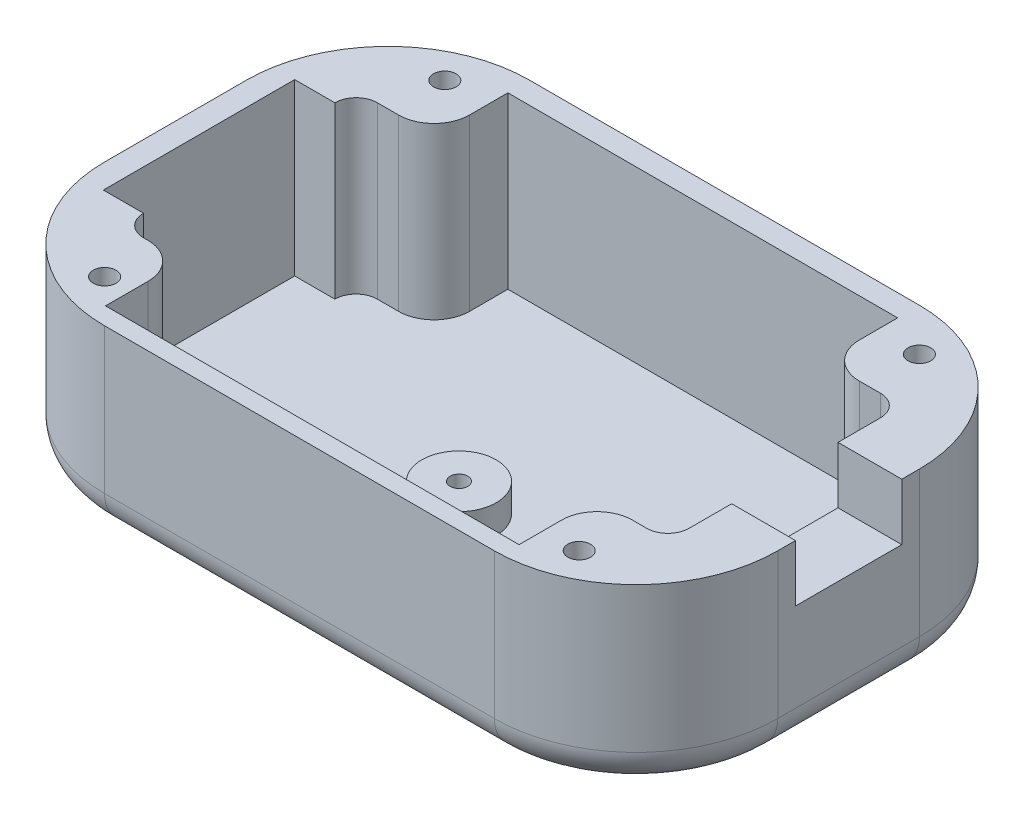
SolidWorks part; units mm, degrees
ref_plane "Front Plane" through (0, 0, 0) normal (0, 0, 1) x (1, 0, 0)
ref_plane "Top Plane" through (0, 0, 0) normal (0, 1, 0) x (1, 0, 0)
ref_plane "Right Plane" through (0, 0, 0) normal (1, 0, 0) x (0, 0, -1)
sketch "Sketch2" plane through (0, 0, 0) normal (0, 1, 0) x (1, 0, 0)
  line L0 (38.5, 0) -> (-38.5, 0) construction
  line L1 (-27.5, 30) -> (27.5, 30)
  line L2 (-47.5, 10) -> (-47.5, -10)
  line L3 (-27.5, -30) -> (27.5, -30)
  line L4 (47.5, 10) -> (47.5, -10)
  line L5 (-47.5, 30) -> (47.5, -30) construction
  line L6 (-47.5, -30) -> (47.5, 30) construction
  line L7 (-35.5, 16.5) -> (35.5, 16.5)
  line L8 (-38.5, 13.5) -> (-38.5, -13.5)
  line L9 (-35.5, -16.5) -> (35.5, -16.5)
  line L10 (38.5, 13.5) -> (38.5, -13.5)
  line L11 (-38.5, 16.5) -> (38.5, -16.5) construction
  line L12 (-38.5, -16.5) -> (38.5, 16.5) construction
  line L13 (0, 0) -> (0, 8.176) construction
  line L15 (-12, -27.5) -> (12, -27.5)
  line L16 (-12, -27.5) -> (-12, -13.5)
  line L17 (-12, -13.5) -> (12, -13.5)
  line L18 (12, -27.5) -> (12, -13.5)
  line L19 (-12, -27.5) -> (12, -13.5) construction
  line L20 (-12, -13.5) -> (12, -27.5) construction
  arc A0 (27.5, 30) -> (47.5, 10) centre (27.5, 10) cw
  arc A1 (27.5, -30) -> (47.5, -10) centre (27.5, -10) ccw
  arc A2 (-47.5, -10) -> (-27.5, -30) centre (-27.5, -10) ccw
  arc A3 (-27.5, 30) -> (-47.5, 10) centre (-27.5, 10) ccw
  arc A4 (35.5, 16.5) -> (38.5, 13.5) centre (35.5, 13.5) cw
  arc A5 (35.5, -16.5) -> (38.5, -13.5) centre (35.5, -13.5) ccw
  arc A6 (-38.5, -13.5) -> (-35.5, -16.5) centre (-35.5, -13.5) ccw
  arc A7 (-35.5, 16.5) -> (-38.5, 13.5) centre (-35.5, 13.5) ccw
  circle A8 centre (22, -4) radius 1.25
  circle A9 centre (-3.4806, -4) radius 1.25
  circle A10 centre (-33.4806, 24) radius 1.6
  circle A11 centre (33.4806, 24) radius 1.6
  circle A12 centre (33.4806, -24) radius 1.6
  circle A13 centre (-33.4806, -24) radius 1.6
  point P0 (0, 0)
  point P18 (0, 0)
  point P55 (0, -20.5)
  point P56 (0, 0)
  point P57 (0, 0)
  point P58 (-3.4806, -3.4011)
  point P59 (22, -4.4636)
  point P62 (16.1275, -4.7534)
  dimension "D3" = 20
  dimension "D6" = 3
  dimension "D7" = 2.5
  dimension "D9" = 2.5
  dimension "D11" = 3.2
  dimension "D18" = 4
  dimension "D1" = 60
  dimension "D2" = 95
  dimension "D4" = 33
  dimension "D5" = 77
  dimension "D8" = 16.5
  dimension "D10" = 4
  dimension "D12" = 24
  dimension "D13" = 30
  dimension "D14" = 24
  dimension "D15" = 14
  dimension "D16" = 12
  dimension "D17" = 2.5
  dimension "D19" = 25.4806
extrude "Boss-Extrude1" add sketch "Sketch2" along normal blind 1.5 contours L1 A3 L2 A2 L3 A1 L4 A0 A11 A10 A7 L7 A4 L10 A5 L9 L18 L15 L16 A6 L8 A12 A13 | L15 L18 L9 L16 | L9 L18 L17 L16 | L7 A7 L8 A6 L9 L16 L17 L18 A5 L10 A4 A9 A8 region at (0, 0, -28.8764) region at (-0.0371, 0, -0.4566) region at (0, 0, 15) region at (0, 0, 22)
extrude "Boss-Extrude2" add sketch "Sketch2<3>" along normal blind 24 from surface contours L1 A3 L2 A2 L3 A1 L4 A0 A11 A10 A7 L7 A4 L10 A5 L9 L18 L15 L16 A6 L8 A12 A13 region at (0, 0, -28.8764) starting at face at (33.4806, 1.5, -22.4)
sketch "Sketch2<3>" plane through (0, 0, 0) normal (0, 1, 0) x (1, 0, 0) same geometry as "Sketch2"
sketch "Sketch3" plane through (0, 1.5, 0) normal (0, 1, 0) x (1, 0, 0)
  circle A2 centre (-3.4806, -4) radius 5.25
  circle A3 centre (-3.4806, -4) radius 5.25
  circle A4 centre (22, -4) radius 1.25 construction
  circle A5 centre (22, -4) radius 5.25
  circle A6 centre (22, -4) radius 5.25
  circle A7 centre (-3.4806, -4) radius 1.25 construction
  circle A8 centre (22, -4) radius 1.25
  circle A9 centre (-3.4806, -4) radius 1.25
  dimension "D1" = 4
  dimension "D2" = 4
extrude "Boss-Extrude3" add sketch "Sketch3" along normal blind 4
fillet "Fillet1" radius 10 2 edges at (12, 13.5, 16.5) (-12, 13.5, 16.5)
sketch "Sketch4" plane through (0, 1.5, 0) normal (0, 1, 0) x (1, 0, 0)
  line L0 (0, -27.5) -> (0, -11.9552) construction
  line L1 (12, -27.5) -> (-12, -27.5) construction
  line L2 (-7, -17.5) -> (7, -17.5) construction
  line L3 (12, -27.5) -> (-12, -27.5) construction
  circle A0 centre (-7, -17.5) radius 1.3
  circle A1 centre (7, -17.5) radius 1.3
  dimension "D4" = 2.6
  dimension "D5" = 2.6
  dimension "D1" = 14
  dimension "D2" = 10
  dimension "D3" = 7
extrude "Cut-Extrude1" cut sketch "Sketch4" against normal blind 7
sketch "Sketch5" plane through (0, 0, 0) normal (0, -1, 0) x (1, 0, 0)
  circle A2 centre (-33.4806, 24) radius 3.1
  circle A3 centre (-33.4806, 24) radius 3.1
  circle A5 centre (-33.4806, -24) radius 3.1
  circle A6 centre (-33.4806, -24) radius 3.1
  circle A8 centre (33.4806, -24) radius 3.1
  circle A9 centre (33.4806, -24) radius 3.1
  circle A11 centre (33.4806, 24) radius 3.1
  circle A12 centre (33.4806, 24) radius 3.1
  dimension "D1" = 1.5
  dimension "D2" = 1.5
  dimension "D3" = 1.5
  dimension "D4" = 1.5
extrude "Cut-Extrude2" cut sketch "Sketch5" against normal blind 15
fillet "Fillet2" radius 5 8 edges at (-47.5, 0, 0) (-41.6421, 0, -24.1421) (0, 0, -30) (41.6421, 0, -24.1421) (47.5, 0, 0) (41.6421, 0, 24.1421) (0, 0, 30) (-41.6421, 0, 24.1421)
sketch "Sketch6" plane through (47.5, 0, 0) normal (1, 0, 0) x (0, 0, -1)
  line L0 (-30, 17.5) -> (30, 17.5) construction
  line L1 (-30, 25.5) -> (-30, 5) construction
  line L2 (30, 25.5) -> (30, 5) construction
  line L3 (1.25, 5.5) -> (-9.25, 5.5) construction
  line L4 (-30, 26.5) -> (30, 26.5) construction
  line L6 (-7.5, 26.5) -> (7.5, 26.5)
  line L7 (-7.5, 26.5) -> (-7.5, 17.5)
  line L8 (-7.5, 17.5) -> (7.5, 17.5)
  line L9 (7.5, 26.5) -> (7.5, 17.5)
  line L10 (-7.5, 26.5) -> (7.5, 17.5) construction
  line L11 (-7.5, 17.5) -> (7.5, 26.5) construction
  point P14 (0, 22)
  dimension "D1" = 12
  dimension "D2" = 9
  dimension "D3" = 15
  dimension "D4" = 7.5
extrude "Cut-Extrude3" cut sketch "Sketch6" against normal blind 15
sketch "Sketch7" plane through (0, 25.5, 0) normal (0, 1, 0) x (1, 0, 0)
  line L0 (35.5, -16.5) -> (22, -16.5) construction
  line L1 (28.5, -16.5) -> (16.5, -16.5)
  line L2 (28.5, -16.5) -> (28.5, -22.5)
  line L3 (28.5, -22.5) -> (16.5, -22.5)
  line L4 (16.5, -16.5) -> (16.5, -22.5)
  line L5 (28.5, -16.5) -> (16.5, -22.5) construction
  line L6 (28.5, -22.5) -> (16.5, -16.5) construction
  line L7 (38.5, -13.5) -> (38.5, 13.5) construction
  point P4 (22.5, -19.5)
  dimension "D1" = 10
  dimension "D2" = 12
extrude "Cut-Extrude4" cut sketch "Sketch7" against normal blind 15
sketch "Sketch10" plane through (0, 25.5, 0) normal (0, 1, 0) x (1, 0, 0)
  line L1 (-27.5, 16.5) -> (27.5, 16.5)
  line L2 (-27.5, 16.5) -> (-27.5, 26.9174)
  line L3 (-27.5, 26.9174) -> (27.5, 26.9174)
  line L4 (27.5, 16.5) -> (27.5, 26.9174)
  line L5 (-27.5, 16.5) -> (27.5, 26.9174) construction
  line L6 (-27.5, 26.9174) -> (27.5, 16.5) construction
  line L7 (-38.5, 13.5) -> (-44.1621, 13.5)
  line L8 (-38.5, 13.5) -> (-38.5, -13.5)
  line L9 (-38.5, -13.5) -> (-44.1621, -13.5)
  line L10 (-44.1621, 13.5) -> (-44.1621, -13.5)
  line L11 (-38.5, 13.5) -> (-44.1621, -13.5) construction
  line L12 (-38.5, -13.5) -> (-44.1621, 13.5) construction
  line L13 (-29.8564, -16.5) -> (-12, -16.5)
  line L14 (-29.8564, -16.5) -> (-29.8564, -27.5)
  line L15 (-29.8564, -27.5) -> (-12, -27.5)
  line L16 (-12, -16.5) -> (-12, -27.5)
  line L17 (-29.8564, -16.5) -> (-12, -27.5) construction
  line L18 (-29.8564, -27.5) -> (-12, -16.5) construction
  line L19 (28.5, -16.5) -> (28.5, -22.5)
  line L20 (28.5, -22.5) -> (16.5, -22.5)
  line L21 (16.5, -22.5) -> (16.5, -18.1484)
  line L22 (12, -26.5) -> (12, -27.5)
  line L23 (12, -27.5) -> (-12, -27.5)
  line L24 (-12, -27.5) -> (-12, -26.5)
  line L25 (-22, -16.5) -> (-35.5, -16.5)
  line L26 (-38.5, -13.5) -> (-38.5, 13.5)
  line L27 (-35.5, 16.5) -> (35.5, 16.5)
  line L28 (38.5, 13.5) -> (38.5, 7.5)
  line L29 (38.5, 7.5) -> (47.5, 7.5)
  line L30 (47.5, 7.5) -> (47.5, 10)
  line L31 (27.5, 30) -> (-27.5, 30)
  line L32 (-47.5, 10) -> (-47.5, -10)
  line L33 (-27.5, -30) -> (27.5, -30)
  line L34 (47.5, -10) -> (47.5, -7.5)
  line L35 (47.5, -7.5) -> (38.5, -7.5)
  line L36 (38.5, -7.5) -> (38.5, -13.5)
  line L37 (35.5, -16.5) -> (28.5, -16.5)
  line L38 (28.5, -16.5) -> (28.5, -22.5)
  line L39 (28.5, -22.5) -> (16.5, -22.5)
  line L40 (16.5, -22.5) -> (16.5, -18.1484)
  line L41 (12, -26.5) -> (12, -27.5)
  line L42 (12, -27.5) -> (-12, -27.5)
  line L43 (-12, -27.5) -> (-12, -26.5)
  line L44 (-22, -16.5) -> (-35.5, -16.5)
  line L45 (-38.5, -13.5) -> (-38.5, 13.5)
  line L46 (-35.5, 16.5) -> (35.5, 16.5)
  line L47 (38.5, 13.5) -> (38.5, 7.5)
  line L48 (38.5, 7.5) -> (47.5, 7.5)
  line L49 (47.5, 7.5) -> (47.5, 10)
  line L50 (27.5, 30) -> (-27.5, 30)
  line L51 (-47.5, 10) -> (-47.5, -10)
  line L52 (-27.5, -30) -> (27.5, -30)
  line L53 (47.5, -10) -> (47.5, -7.5)
  line L54 (47.5, -7.5) -> (38.5, -7.5)
  line L55 (38.5, -7.5) -> (38.5, -13.5)
  line L56 (35.5, -16.5) -> (28.5, -16.5)
  line L57 (12, -27.5) -> (28.5, -27.5)
  line L58 (12, -27.5) -> (12, -16.5)
  line L59 (12, -16.5) -> (28.5, -16.5)
  line L60 (28.5, -27.5) -> (28.5, -16.5)
  line L61 (12, -27.5) -> (28.5, -16.5) construction
  line L62 (12, -16.5) -> (28.5, -27.5) construction
  arc A10 (16.5, -18.1484) -> (12, -26.5) centre (22, -26.5) ccw
  arc A11 (-12, -26.5) -> (-22, -16.5) centre (-22, -26.5) ccw
  arc A12 (-38.5, -13.5) -> (-35.5, -16.5) centre (-35.5, -13.5) ccw
  arc A13 (-35.5, 16.5) -> (-38.5, 13.5) centre (-35.5, 13.5) ccw
  arc A14 (38.5, 13.5) -> (35.5, 16.5) centre (35.5, 13.5) ccw
  arc A15 (47.5, 10) -> (27.5, 30) centre (27.5, 10) ccw
  arc A16 (-27.5, 30) -> (-47.5, 10) centre (-27.5, 10) ccw
  arc A17 (-47.5, -10) -> (-27.5, -30) centre (-27.5, -10) ccw
  arc A18 (27.5, -30) -> (47.5, -10) centre (27.5, -10) ccw
  arc A19 (35.5, -16.5) -> (38.5, -13.5) centre (35.5, -13.5) ccw
  arc A20 (16.5, -18.1484) -> (12, -26.5) centre (22, -26.5) ccw
  arc A21 (-12, -26.5) -> (-22, -16.5) centre (-22, -26.5) ccw
  arc A22 (-38.5, -13.5) -> (-35.5, -16.5) centre (-35.5, -13.5) ccw
  arc A23 (-35.5, 16.5) -> (-38.5, 13.5) centre (-35.5, 13.5) ccw
  arc A24 (38.5, 13.5) -> (35.5, 16.5) centre (35.5, 13.5) ccw
  arc A25 (47.5, 10) -> (27.5, 30) centre (27.5, 10) ccw
  arc A26 (-27.5, 30) -> (-47.5, 10) centre (-27.5, 10) ccw
  arc A27 (-47.5, -10) -> (-27.5, -30) centre (-27.5, -10) ccw
  arc A28 (27.5, -30) -> (47.5, -10) centre (27.5, -10) ccw
  arc A29 (35.5, -16.5) -> (38.5, -13.5) centre (35.5, -13.5) ccw
  point P17 (0, 21.7087)
  point P27 (-41.331, 0)
  point P51 (-20.9282, -22)
  point P54 (20.25, -22)
  line M30 (28.5, -16.5) -> (28.5, -22.5)
  line M31 (28.5, -22.5) -> (16.5, -22.5)
  line M32 (16.5, -22.5) -> (16.5, -18.1484)
  arc M33 (16.5, -18.1484) -> (12, -26.5) centre (22, -26.5) ccw
  line M34 (12, -26.5) -> (12, -27.5)
  line M36 (-12, -27.5) -> (-12, -26.5)
  arc M37 (-12, -26.5) -> (-22, -16.5) centre (-22, -26.5) ccw
  line M38 (-22, -16.5) -> (-35.5, -16.5)
  line M40 (-38.5, -13.5) -> (-38.5, 13.5)
  line M42 (-35.5, 16.5) -> (35.5, 16.5)
  dimension "D1" = 0
extrude "Cut-Extrude5" cut sketch "Sketch10" against normal up to surface (24 mm away) contours L7 L10 L9 M40 | L4 L3 L2 M42 | L14 L15 M36 M37 M38 | L16 L13 M37 | L59 L58 M33 M32 M31 M30 | L57 L60 M31 M32 M33 M34 region at (0, 25.5, -21.7087) region at (-41.331, 25.5, 0) region at (-21.7493, 25.5, 22.4006) region at (-14.2337, 25.5, 18.7337) region at (19.8115, 25.5, 24.589) region at (20.6904, 25.5, 19.3993) up to face at (-7, 1.5, 18.8)
fillet "Fillet6" radius 5 4 edges at (27.5, 13.5, -16.5) (28.5, 13.5, 16.5) (-29.8564, 13.5, 16.5) (-27.5, 13.5, -16.5)
